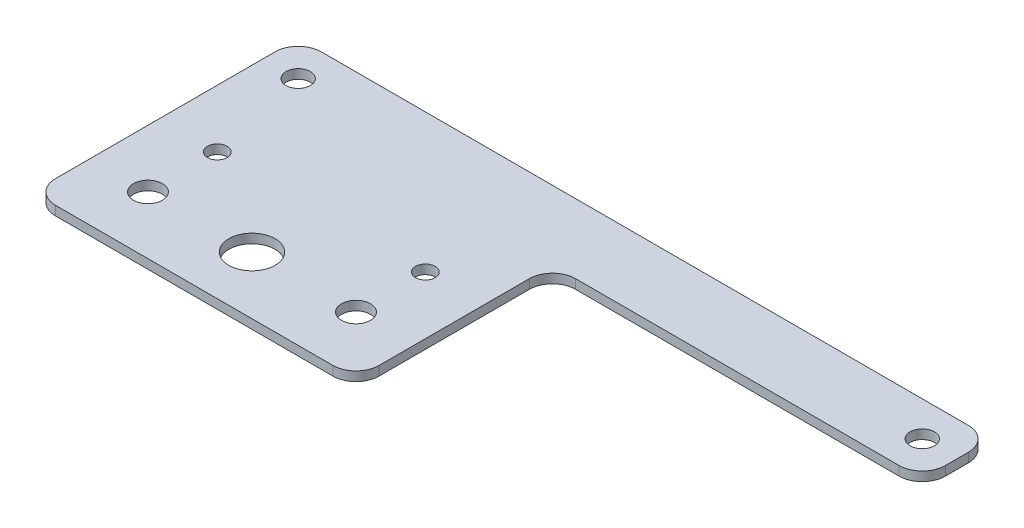
SolidWorks part; units mm, degrees
material "ASTM A36 Steel"
ref_plane "Front Plane" through (0, 0, 0) normal (0, 0, 1) x (1, 0, 0)
ref_plane "Top Plane" through (0, 0, 0) normal (0, 1, 0) x (1, 0, 0)
ref_plane "Right Plane" through (0, 0, 0) normal (1, 0, 0) x (0, 0, -1)
sketch "Sketch1" plane through (0, 0, 0) normal (0, 1, 0) x (1, 0, 0)
  line L1 (70, -42.5) -> (-70, -42.5)
  line L2 (70, -42.5) -> (70, 42.5)
  line L4 (-70, -42.5) -> (-70, 42.5)
  line L5 (70, -42.5) -> (-70, 42.5) construction
  line L6 (70, 42.5) -> (-70, -42.5) construction
  line L7 (70, 42.5) -> (230, 42.5)
  line L8 (-70, 42.5) -> (-70, 72.5)
  line L9 (-70, 72.5) -> (230, 72.5)
  line L10 (230, 42.5) -> (230, 72.5)
  circle A0 centre (-55, 57.5) radius 5.25
  circle A1 centre (215, 57.5) radius 5.25
  circle A2 centre (0, -17.5) radius 10
  circle A3 centre (-45, -17.5) radius 6.25
  circle A4 centre (45, -17.5) radius 6.25
  circle A5 centre (-45, 12.5) radius 4.25
  circle A6 centre (45, 12.5) radius 4.25
  point P0 (0, 0)
  dimension "D6" = 10.5
  dimension "D10" = 10.5
  dimension "D11" = 20
  dimension "D13" = 12.5
  dimension "D14" = 12.5
  dimension "D17" = 8.5
  dimension "D18" = 8.5
  dimension "D1" = 140
  dimension "D2" = 300
  dimension "D3" = 30
  dimension "D4" = 85
  dimension "D5" = 42.5
  dimension "D7" = 15
  dimension "D8" = 15
  dimension "D9" = 15
  dimension "D12" = 25
  dimension "D15" = 45
  dimension "D16" = 45
  dimension "D19" = 30
  dimension "D20" = 45
  dimension "D21" = 45
base flange "Base-Flange1" sketch "Sketch1" thickness 4 reverse thickness direction no parameters "D1"=10
fillet "Fillet1" radius 10 6 edges at (230, -2, -42.5) (230, -2, -72.5) (-70, -2, -72.5) (-70, -2, 42.5) (70, -2, 42.5) (70, -2, -42.5)
sketch "Bend-Lines1" [suppressed] plane through (0, 0, 0) normal (0, 1, 0) x (1, 0, 0)
sketch "Bounding-Box1" [suppressed] plane through (0, 0, 0) normal (0, 1, 0) x (1, 0, 0)
sheet metal parameters "Sheet-Metal1" thickness 4 parameters "D1"=10
flat pattern "Flat-Pattern1" [suppressed]
sketch "Bend-Lines2" plane through (0, 0, 0) normal (0, 1, 0) x (1, 0, 0)
sketch3d "Bounding-Box2" [suppressed]
  line L0 (-70, 72.5, 0) -> (230, 72.5, 0) construction
  line L1 (-70, -42.5, 0) -> (230, -42.5, 0) construction
  line L2 (-70, 72.5, 0) -> (-70, -42.5, 0) construction
  line L3 (230, 72.5, 0) -> (230, -42.5, 0) construction
